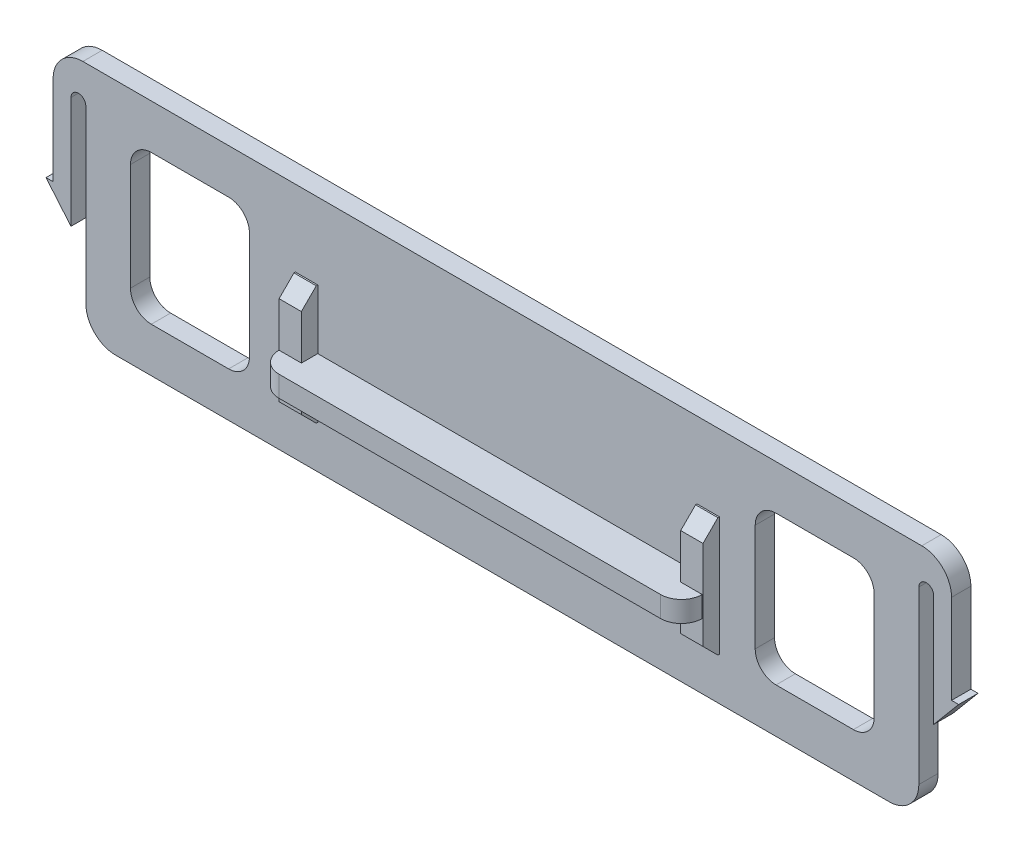
SolidWorks part; units mm, degrees
ref_plane "前视基准面" through (0, 0, 0) normal (0, 0, 1) x (1, 0, 0)
ref_plane "上视基准面" through (0, 0, 0) normal (0, 1, 0) x (1, 0, 0)
ref_plane "右视基准面" through (0, 0, 0) normal (1, 0, 0) x (0, 0, -1)
sketch "草图1" plane through (0, 0, 0) normal (0, 0, 1) x (1, 0, 0)
  line L1 (-28, 8) -> (28, 8)
  line L2 (-28, 8) -> (-28, -8)
  line L3 (-28, -8) -> (28, -8)
  line L4 (28, 8) -> (28, -8)
  line L5 (-28, 8) -> (28, -8) construction
  line L6 (-28, -8) -> (28, 8) construction
  point P0 (0, 0)
  dimension "D1" = 56
  dimension "D2" = 16
extrude "凸台-拉伸1" add sketch "草图1" along normal blind 1.3
sketch "草图2" plane through (0, 0, 1.3) normal (0, 0, 1) x (1, 0, 0)
  line L9 (28, 8) -> (30.2, 8)
  line L10 (30.2, 8) -> (30.2, 0)
  line L11 (30.2, 0) -> (31, 0)
  line L12 (31, 0) -> (31, -2)
  line L13 (31, -2) -> (29, -2)
  line L14 (29, -2) -> (29, 6)
  line L15 (29, 6) -> (28, 6)
  line L16 (28, -8) -> (28, 8) construction
  line L17 (28, 6) -> (28, 8)
  line L20 (-28, 8) -> (-30.2, 8)
  line L21 (-30.2, 8) -> (-30.2, 0)
  line L22 (-30.2, 0) -> (-31, 0)
  line L23 (-31, 0) -> (-31, -2)
  line L24 (-31, -2) -> (-29, -2)
  line L25 (-29, -2) -> (-29, 6)
  line L26 (-29, 6) -> (-28, 6)
  line L27 (-28, 8) -> (-28, -8) construction
  line L28 (-28, 6) -> (-28, 8)
  dimension "D1" = 8
  dimension "D2" = 2
  dimension "D3" = 2
  dimension "D4" = 0.8
  dimension "D5" = 2.2
  dimension "D6" = 0.8
  dimension "D7" = 2.2
  dimension "D8" = 8
  dimension "D9" = 2
  dimension "D10" = 2
  dimension "D11" = 2
  dimension "D12" = 2
extrude "凸台-拉伸2" add sketch "草图2" against normal up to surface (1.3 mm away) up to face at (0, 0, 0)
fillet "圆角1" radius 2 4 edges at (30.2, 8, 0.65) (28, -8, 0.65) (-28, -8, 0.65) (-30.2, 8, 0.65)
fillet "圆角2" radius 0.5 4 edges at (28, 6, 0.65) (29, 6, 0.65) (-28, 6, 0.65) (-29, 6, 0.65)
chamfer "倒角1" distance 2 angle 50 1 edges at (31, -2, 0.65) first distance on face at (30, -2, 0.65)
chamfer "倒角2" distance 2 angle 50 1 edges at (-31, -2, 0.65) first distance on face at (-30, -2, 0.65)
sketch "草图3" plane through (0, 0, 1.3) normal (0, 0, 1) x (1, 0, 0)
  line L1 (-13.9089, 2.8832) -> (-12.4089, 2.8832)
  line L2 (-13.9089, 2.8832) -> (-13.9089, -5.1168)
  line L3 (-13.9089, -5.1168) -> (-12.4089, -5.1168)
  line L4 (-12.4089, 2.8832) -> (-12.4089, -5.1168)
  line L5 (13.0911, -5.1168) -> (14.5911, -5.1168)
  line L6 (13.0911, -5.1168) -> (13.0911, 2.8832)
  line L7 (13.0911, 2.8832) -> (14.5911, 2.8832)
  line L8 (14.5911, -5.1168) -> (14.5911, 2.8832)
extrude "凸台-拉伸3" add sketch "草图3" along normal blind 1.1
chamfer "倒角3" distance 1 angle 45 4 edges at (13.8411, -5.1168, 2.4) (-13.1589, -5.1168, 2.4) (13.8411, 2.8832, 2.4) (-13.1589, 2.8832, 2.4)
sketch "草图4" plane through (0, 0, 1.3) normal (0, 0, 1) x (1, 0, 0)
  line L0 (-13.9089, 1.8832) -> (-13.9089, -4.1168) construction
  line L1 (-13.9089, -1.1168) -> (14.5366, -1.1168)
  line L2 (-13.9089, -1.1168) -> (-13.9089, -2.5168)
  line L3 (-13.9089, -2.5168) -> (14.5366, -2.5168)
  line L4 (14.5366, -1.1168) -> (14.5366, -2.5168)
extrude "凸台-拉伸4" add sketch "草图4" along normal blind 2.5
fillet "圆角3" radius 1.4 2 edges at (14.5366, -1.8168, 3.8) (-13.9089, -1.8168, 3.8)
sketch "草图6" plane through (0, 0, 1.3) normal (0, 0, 1) x (1, 0, 0)
  line L0 (-28, 5.5) -> (-28, -6) construction
  line L1 (-25, 5) -> (-17, 5)
  line L2 (-25, 5) -> (-25, -5)
  line L3 (-25, -5) -> (-17, -5)
  line L4 (-17, 5) -> (-17, -5)
  line L5 (-25, 5) -> (-17, -5) construction
  line L6 (-25, -5) -> (-17, 5) construction
  line L7 (17, 5) -> (25, 5)
  line L8 (17, 5) -> (17, -5)
  line L9 (17, -5) -> (25, -5)
  line L10 (25, 5) -> (25, -5)
  line L11 (17, 5) -> (25, -5) construction
  line L12 (17, -5) -> (25, 5) construction
  line L13 (28, -6) -> (28, 5.5) construction
  line L14 (28.2, 8) -> (-28.2, 8) construction
  point P0 (-21, 0)
  point P5 (21, 0)
  point P16 (0, 0)
  dimension "D1" = 7
  dimension "D2" = 7
  dimension "D3" = 8
  dimension "D4" = 8
  dimension "D5" = 10
  dimension "D6" = 10
  dimension "D7" = 8
  dimension "D8" = 8
extrude "切除-拉伸1" cut sketch "草图6" against normal up to next
fillet "圆角4" radius 1.4 8 edges at (25, 5, 0.65) (17, 5, 0.65) (25, -5, 0.65) (17, -5, 0.65) (-17, -5, 0.65) (-25, -5, 0.65) (-17, 5, 0.65) (-25, 5, 0.65)
